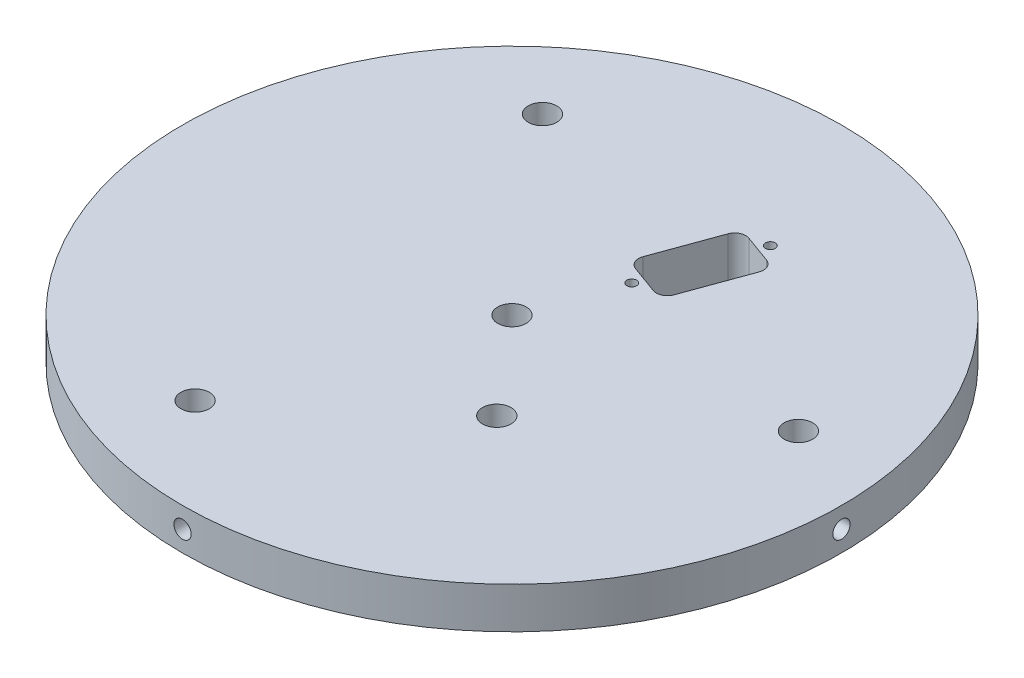
SolidWorks part; units mm, degrees
material "6061-T6 (SS)"
ref_plane "Front Plane" through (0, 0, 0) normal (0, 0, 1) x (1, 0, 0)
ref_plane "Top Plane" through (0, 0, 0) normal (0, 1, 0) x (1, 0, 0)
ref_plane "Right Plane" through (0, 0, 0) normal (1, 0, 0) x (0, 0, -1)
sketch "Sketch1" plane through (0, 0, 0) normal (0, 1, 0) x (1, 0, 0)
  line L0 (0, 0) -> (-50.3682, 60.0265)
  line L1 (0, 0) -> (50.3682, 60.0265)
  line L2 (0, 0) -> (0, 72.1431) construction
  circle A0 centre (0, 0) radius 78.359
  circle A1 centre (0, 0) radius 76.1746
  circle A2 centre (0, 0) radius 76.1746
  dimension "D1" = 156.718
  dimension "D2" = 152.3492
  dimension "D3" = 152.3492
  dimension "D4" = 80
extrude "Boss-Extrude1" add sketch "Sketch1" along normal blind 25.4 contours L2 A2 L1 A0 | L2 A1 L1 A2 | L2 A2 L1 A1 | L2 A0 L1 A2 | A2 L2 A1 L0 | A0 L2 A2 L0 | A2 L2 A0 L0 | A1 L2 A2 L0 region at (0, 0, 13.3592) region at (-23.5316, 0, -29.974) region at (-33.0764, 0, 70.9325) region at (-48.8794, 0, -59.85)
ref_plane "Plane1" through (0, 12.7, 0) normal (0, 1, 0) x (1, 0, 0)
sketch "Sketch6" plane through (0, 25.4, 0) normal (0, 1, 0) x (1, 0, 0)
  circle A0 centre (0, 0) radius 76.1746
  dimension "D1" = 152.3492
extrude "Boss-Extrude5" add sketch "Sketch6" along normal blind 9.525
sketch "Sketch7" plane through (0, 0, 0) normal (0, -1, 0) x (1, 0, 0)
  circle A0 centre (0, 0) radius 76.1746
  dimension "D1" = 152.3492
extrude "Boss-Extrude6" add sketch "Sketch7" along normal blind 9.525
sketch "Sketch8" plane through (0, -9.525, 0) normal (0, -1, 0) x (1, 0, 0)
  circle A0 centre (0, 0) radius 73.025
  dimension "D1" = 146.05
extrude "Cut-Extrude5" cut sketch "Sketch8" against normal up to surface (34.925 mm away) up to face at (0, 25.4, 76.1746)
ref_plane "Plane2" through (0, 0, -76.1746) normal (0, 0, -1) x (-1, 0, 0)
ref_plane "Plane5" through (0, 25.4, 0) normal (0, 1, 0) x (1, 0, 0)
ref_axis "Axis1" through (0, 0, 0) along (0, 1, 0)
sketch "Sketch3" plane through (0, 0, -76.1746) normal (0, 0, -1) x (-1, 0, 0)
  line L4 (76.1746, 0) -> (-76.1746, 0)
  line L5 (-76.1746, -9.525) -> (76.1746, -9.525)
  line L6 (76.1746, 25.4) -> (-76.1746, 25.4)
  line L7 (76.1746, 34.925) -> (-76.1746, 34.925)
  line L8 (0, 34.925) -> (0, 25.4) construction
  line L9 (0, 0) -> (0, -9.525) construction
  circle A0 centre (0, 30.1625) radius 2
  circle A1 centre (0, -4.7625) radius 2
  point P12 (0, 30.1625)
  point P13 (0, -4.7625)
  point P14 (-77.5445, 179.1871)
  dimension "D1" = 4
extrude "Cut-Extrude2" cut sketch "Sketch3" against normal blind 9.525 contours L8 A0 | L8 A0 | L9 A1 | L9 A1 region at (0, 30.1625, -76.1746) region at (0, -4.7625, -76.1746)
extrude "Cut-Extrude3" cut sketch "Sketch1<7>" against normal blind 9.525 from surface contours L2 A1 L1 A2 | A1 L2 A2 L0 | A2 L2 A0 L0 | L2 A2 L1 A0 region at (-23.5316, 0, -29.974) region at (-48.8794, 0, -59.85) starting at plane "Plane5"
sketch "Sketch1<7>" plane through (0, 0, 0) normal (0, 1, 0) x (1, 0, 0) same geometry as "Sketch1"
pattern_circular "CirPattern2" count 3 over 360 about axis through (0, 0, 0) along (0, 1, 0) of "Cut-Extrude3"
ref_plane "Plane3" through (0, 34.925, 0) normal (0, 1, 0) x (1, 0, 0)
sketch "Sketch4" plane through (0, 34.925, 0) normal (0, 1, 0) x (1, 0, 0)
  circle A0 centre (0, 0) radius 73.025
  dimension "D1" = 146.05
extrude "Boss-Extrude4" add sketch "Sketch4" against normal blind 9.525
pattern_circular "CirPattern3" count 4 over 360 about axis through (0, 0, 0) along (0, 1, 0) of "Cut-Extrude2"
sketch "Sketch9" plane through (0, 34.925, 0) normal (0, 1, 0) x (1, 0, 0)
  line L0 (0, 0) -> (-26.8004, -73.6334) construction
  line L1 (0, 0) -> (32.0596, -38.2071) construction
  circle A0 centre (0, 0) radius 3.3
  circle A1 centre (-19.5465, -53.7034) radius 3.3
  circle A2 centre (-36.7353, 43.7794) radius 3.3
  circle A3 centre (56.2818, 9.924) radius 3.3
  circle A4 centre (18.3677, -21.8897) radius 3.3
  point P15 (0, 0)
  dimension "D1" = 6.6
  dimension "D2" = 6.6
  dimension "D6" = 6.6
  dimension "D3" = 57.15
  dimension "D4" = 60
  dimension "D7" = 28.575
extrude "Cut-Extrude6" cut sketch "Sketch9" against normal through all
sketch "Sketch10" plane through (0, 25.4, 0) normal (0, 1, 0) x (1, 0, 0)
  circle A0 centre (0, 0) radius 82.3228
extrude "Cut-Extrude7" cut sketch "Sketch10" against normal through all
hole_wizard "Tap Drill for #4-40 Tap1" positions "Sketch12" profile "Sketch13" hole size "#4-40" standard "ANSI Inch" end condition through all
sketch "Sketch12" plane through (0, 34.925, 0) normal (0, 1, 0) x (1, 0, 0)
  line L0 (0, 0) -> (18.6243, 51.1699) construction
  line L2 (0, 0) -> (-36.7353, 43.7794) construction
  circle A0 centre (0, 0) radius 21.59 construction
  point P0 (7.3842, 20.288)
  point P2 (15.9347, 43.7803)
  dimension "D3" = 43.18
  dimension "D1" = 60
  dimension "D2" = 25
sketch "Sketch13" plane through (7.3842, 34.925, -20.288) normal (1, 0, 0) x (0, 0, 1)
  line L0 (0, 0) -> (0, 9.525)
  line L1 (0, 9.525) -> (1.1303, 9.525)
  line L2 (1.1303, 9.525) -> (1.1303, 0)
  line L5 (1.1303, 0) -> (0, 0)
  line L11 (0, -6.35) -> (0, 107.95) construction
  dimension "Thru Hole Dia." = 2.2606
  dimension "Thru Hole Depth" = 9.525
sketch "Sketch14" plane through (0, 34.925, 0) normal (0, 1, 0) x (1, 0, 0)
  line L0 (7.3842, 20.288) -> (15.9347, 43.7803) construction
  line L1 (14.6438, 22.7814) -> (19.8932, 37.2038)
  line L2 (11.3883, 21.2633) -> (4.9439, 23.6089)
  line L3 (18.3751, 40.4594) -> (11.9307, 42.8049)
  line L4 (3.4258, 26.8644) -> (8.6751, 41.2868)
  arc A0 (19.8932, 37.2038) -> (18.3751, 40.4594) centre (17.5063, 38.0725) ccw
  arc A1 (11.9307, 42.8049) -> (8.6751, 41.2868) centre (11.0619, 40.4181) ccw
  arc A2 (11.3883, 21.2633) -> (14.6438, 22.7814) centre (12.257, 23.6501) ccw
  arc A3 (4.9439, 23.6089) -> (3.4258, 26.8644) centre (5.8126, 25.9957) cw
  point P0 (8.1661, 22.4361)
  dimension "D4" = 2.54
  dimension "D5" = 2.54
  dimension "D1" = 2.286
  dimension "D2" = 2.286
  dimension "D3" = 11.938
extrude "Cut-Extrude9" cut sketch "Sketch14" against normal through all
equation "\"AB_Coupler_OD_Length\"= 1in"
equation "\"AB_Coupling_Section_Length\"= 0.375in"
equation "\"AB_Coupler_Length\"= \"AB_Coupler_OD_Length\" + \"AB_Coupling_Section_Length\" * 2"
equation "\"Cutout_Angle\" = 80"
equation "\"AB_Coupler_Num_Screws\"= 6"
equation "\"Num_Cutouts\" = 3"
equation "\"AB_Coupler_OD\"= 6.17in"
equation "\"AB_Coupler_ID\"= 5.75in"
equation "\"AB_Coupler_Surface_Diameter\"= 5.998in"
equation "\"D2@Sketch1\"=\"Bodytube_ID\""
equation "\"AB_Coupling_Screw_Diameter\"= 0.1065in"
equation "\"Aft_Section_Length\"= 39in"
equation "\"Aft_Lower_Length\"= 22in"
equation "\"Aft_Upper_Length\"= \"Aft_Section_Length\" - \"Aft_Lower_Length\" - \"AB_Coupler_OD_Length\""
equation "\"Mid_Coupler_Length\" = 13in"
equation "\"Lead_Screw_Dist\" = 3.4in"
equation "\"Lead_Screw_Diam\" = 0.386in"
equation "\"Lead_Screw_Length\" = (\"Mid_Coupler_Length\" + 2*0.375in + 2*0.5in)"
equation "\"Bodytube_OD\" = 6.17in"
equation "\"Paddle_Pin_Offset\" = .25in"
equation "\"Bodytube_ID\" = 5.998in"
equation "\"Paddle_Pin_Radius\" = 2.25in"
equation "\"D1@Sketch4\"=\"AB_Coupler_ID\""
equation "\"D1@Sketch6\"=\"AB_Coupler_Surface_Diameter\""
equation "\"D1@Boss-Extrude5\"=\"AB_Coupling_Section_Length\""
equation "\"D1@Sketch7\"=\"AB_Coupler_Surface_Diameter\""
equation "\"D1@Boss-Extrude6\"=\"AB_Coupling_Section_Length\""
equation "\"D1@Sketch8\"=\"AB_Coupler_ID\""
equation "\"D3@Sketch9\"=\"Paddle_Pin_Radius\""
equation "\"Motor_OD\" = 4in"
equation "\"Fwd_Tube_Length\" = 40in"
equation "\"Mid_Tube_Length\" = 1in"
equation "\"AB_Paddle_Height\" = 0.375in"
equation "\"AB_Central_Bushing_Length\" = .75in"
equation "\"Paddle_Gear_OD\" = 3.2in"
equation "\"Fwd_BKHD_From_Top\" = 18in"
equation "\"Fin_Thickness\"= .118in"
equation "\"Guiderail_Cutout_Diameter\"= 1.5in"
equation "\"DB9_Hole_Dist\" = 25mm"
equation "\"D2@Sketch12\"=\"DB9_Hole_Dist\""
equation "\"Drive_Gear_OD\" = 1.7in"
equation "\"D3@Sketch12\"=\"Drive_Gear_OD\""
equation "\"DB9_Relief_Width\" = 0.47in"
equation "\"D3@Sketch14\"=\"DB9_Relief_Width\""
equation "\"DB9_Relief_Hole_Offset\" = 0.09in"
equation "\"D2@Sketch14\"=\"DB9_Relief_Hole_Offset\""
equation "\"D1@Sketch14\"=\"DB9_Relief_Hole_Offset\""
equation "\"SS_Paddle_Pin_Radius\" = 2.25*0.66in"
equation "\"Airbrakes_Wire_Hole_Dia\" = .25in"
equation "\"Airbrakes_Wire_Hole_Dist\" = 1.1in"
equation "\"Servo_Gear_Offset\" = 0.5in"
